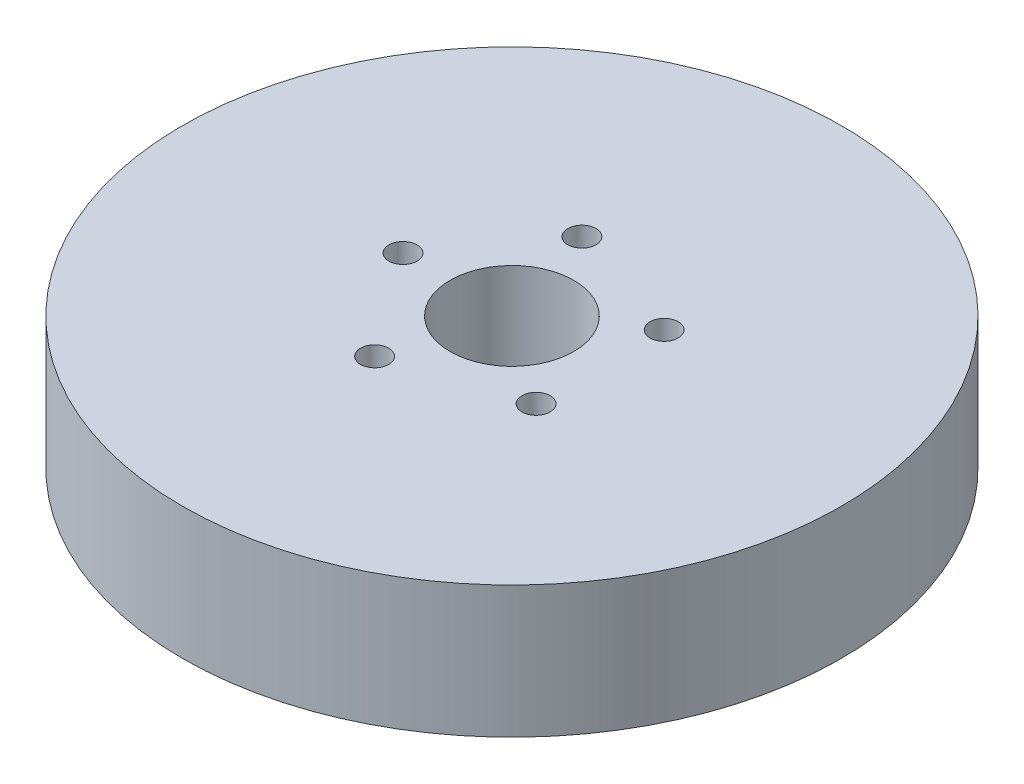
SolidWorks part; units mm, degrees
ref_plane "Front Plane" through (0, 0, 0) normal (0, 0, 1) x (1, 0, 0)
ref_plane "Top Plane" through (0, 0, 0) normal (0, 1, 0) x (1, 0, 0)
ref_plane "Right Plane" through (0, 0, 0) normal (1, 0, 0) x (0, 0, -1)
sketch "Sketch1" plane through (0, 0, 0) normal (0, 1, 0) x (1, 0, 0)
  circle A0 centre (0, 0) radius 40
  dimension "FLANGE_OD" = 80
extrude "Boss-Extrude1" add sketch "Sketch1" along normal blind 16
sketch "Sketch2" plane through (0, 0, 0) normal (0, 1, 0) x (1, 0, 0)
  circle A0 centre (0, 0) radius 7.5
  dimension "BORE_D" = 15
extrude "Cut-Extrude1" cut sketch "Sketch2" along normal through all
sketch "Sketch3" plane through (0, 16, 0) normal (0, 1, 0) x (1, 0, 0)
  circle A0 centre (0, 0) radius 13.2263 construction
  circle A1 centre (-13.2263, 0) radius 1.7109
  dimension "BOLT_D" = 3.4218
  dimension "BOLT_PCD" = 26.4525
extrude "Cut-Extrude2" cut sketch "Sketch3" against normal blind 10.8151
pattern_circular "CirPattern1" count 5 over 360 about axis through (0, 0, 0) along (0, 1, 0) of "Cut-Extrude2"
